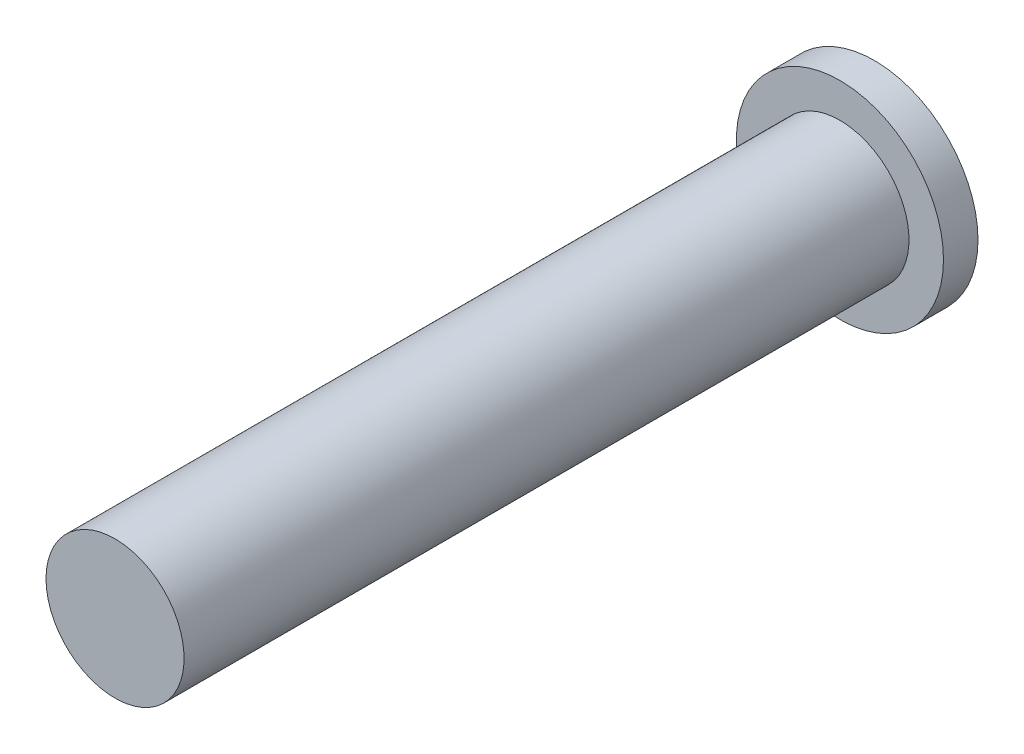
SolidWorks part; units mm, degrees
ref_plane "Plan de face" through (0, 0, 0) normal (0, 0, 1) x (1, 0, 0)
ref_plane "Plan de dessus" through (0, 0, 0) normal (0, 1, 0) x (1, 0, 0)
ref_plane "Plan de droite" through (0, 0, 0) normal (1, 0, 0) x (0, 0, -1)
sketch "Esquisse1" plane through (0, 0, 0) normal (0, 0, 1) x (1, 0, 0)
  circle A0 centre (0, 0) radius 3
  circle A1 centre (0, 0) radius 2
  dimension "D1" = 4
  dimension "D2" = 6
extrude "Boss.-Extru.1" add sketch "Esquisse1" along normal blind 21 contours A1 region at (0, 0, 0)
extrude "Boss.-Extru.2" add sketch "Esquisse1<3>" against normal blind 1 contours A0 A1 | A1 region at (-2.9151, 0, 0) region at (0, 0, 0)
sketch "Esquisse1<3>" plane through (0, 0, 0) normal (0, 0, 1) x (1, 0, 0) same geometry as "Esquisse1"
